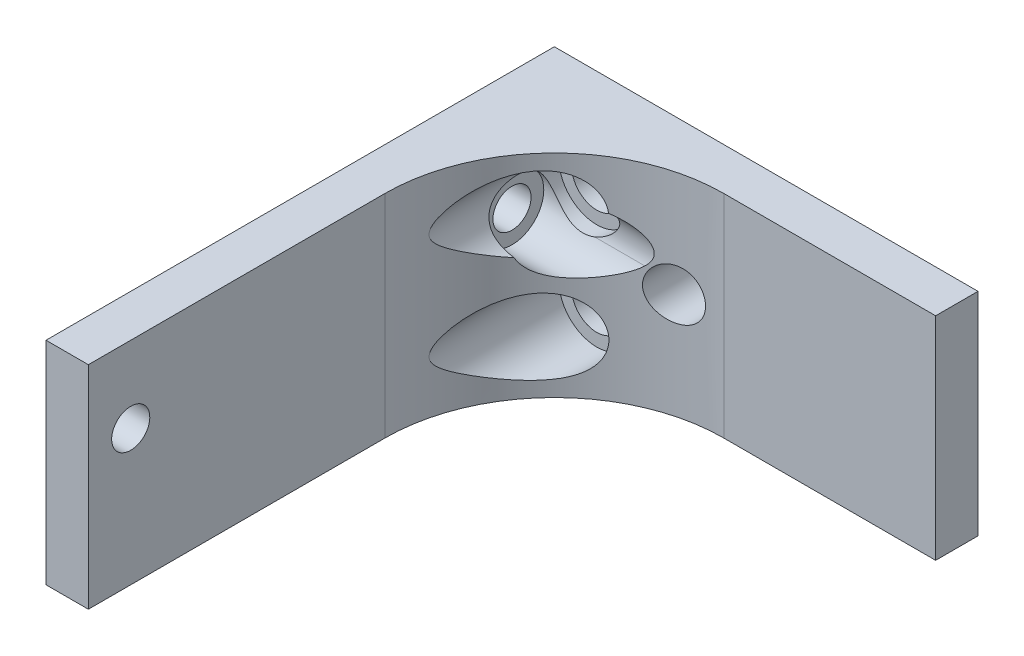
SolidWorks part; units mm, degrees
ref_plane "Alzado" through (0, 0, 0) normal (0, 0, 1) x (1, 0, 0)
ref_plane "Planta" through (0, 0, 0) normal (0, 1, 0) x (1, 0, 0)
ref_plane "Vista lateral" through (0, 0, 0) normal (1, 0, 0) x (0, 0, -1)
sketch "Croquis1" plane through (0, 0, 0) normal (0, 0, 1) x (1, 0, 0)
  line L0 (10, 18.75) -> (10, 6.25) construction
  line L1 (0, 0) -> (50, 0)
  line L2 (0, 0) -> (0, 25)
  line L3 (0, 25) -> (50, 25)
  line L4 (50, 0) -> (50, 25)
  line L6 (0, 25) -> (5, 25)
  line L7 (0, 25) -> (0, 0)
  line L8 (0, 0) -> (5, 0)
  line L9 (5, 25) -> (5, 0)
  circle A0 centre (10, 18.75) radius 2.95
  circle A1 centre (10, 6.25) radius 2.95
  circle A2 centre (20, 12.5) radius 2.95
  point P12 (10, 12.5)
  point P13 (0, 12.5)
  dimension "D3" = 5.9
  dimension "D5" = 10
  dimension "D1" = 50
  dimension "D2" = 25
  dimension "D4" = 12.5
  dimension "D6" = 10
  dimension "D7" = 5
extrude "Saliente-Extruir1" add sketch "Croquis1" along normal blind 5 contours L3 L9 L1 L4 A2 A0 A1 | L9 L3 L2 L1 region at (2.5, 12.5, 0) region at (28.6141, 12.5, 0)
extrude "Saliente-Extruir2" add sketch "Croquis1<3>" along normal blind 60 contours L9 L3 L2 L1 region at (2.5, 12.5, 0)
sketch "Croquis1<3>" plane through (0, 0, 0) normal (0, 0, 1) x (1, 0, 0) same geometry as "Croquis1"
ref_plane "Plano1" through (0, 12.5, 0) normal (0, 1, 0) x (1, 0, 0)
sketch "Croquis2" [suppressed] plane through (0, 12.5, 0) normal (0, 1, 0) x (1, 0, 0)
  line L0 (10, -5) -> (35, -5)
  line L1 (10, -5) -> (50, -5) construction
  line L2 (35, -5) -> (10, -40)
  line L3 (10, -60) -> (10, -5) construction
  line L4 (10, -40) -> (10, -5)
  dimension "D1" = 35
  dimension "D2" = 25
extrude "Saliente-Extruir3" [suppressed] add sketch "Croquis2" along normal blind 2.5 and the other way blind 2.5
sketch "Croquis3" plane through (0, 0, 5) normal (0, 0, 1) x (1, 0, 0)
  circle A0 centre (20, 12.5) radius 2.95 construction
  circle A1 centre (20, 12.5) radius 2.95
extrude "Cortar-Extruir-Lámina2" [suppressed] cut sketch "Croquis3" along normal through all thin thin type mid plane wall 1.5
fillet "Redondeo2" radius 20 1 edges at (5, 12.5, 5)
sketch "Croquis4" plane through (0, 0, 5) normal (0, 0, 1) x (1, 0, 0)
  arc A3 (14.45, 18.75) -> (14.45, 18.75) centre (10, 18.75) ccw
  circle A5 centre (10, 18.75) radius 4.45
  arc A8 (14.45, 6.25) -> (14.45, 6.25) centre (10, 6.25) ccw
  circle A9 centre (10, 6.25) radius 4.45
  dimension "D1" = 1.5
  dimension "D2" = 1.5
extrude "Cortar-Extruir1" cut sketch "Croquis4" along normal through all
sketch "Croquis5" plane through (5, 0, 0) normal (1, 0, 0) x (0, 0, -1)
  line L0 (-12.25, 16) -> (-60, 16) construction
  line L1 (-60, 25) -> (-60, 0) construction
  line L4 (-60, 0) -> (-25, 0)
  line L5 (-60, 0) -> (-25, 0)
  line L6 (-25, 25) -> (-60, 25)
  line L7 (-60, 25) -> (-60, 0)
  line L10 (-25, 25) -> (-60, 25) construction
  line L11 (-60, 25) -> (-60, 0) construction
  line L14 (-25, 0) -> (-25, 25)
  line L15 (-25, 0) -> (-25, 25)
  circle A0 centre (-55, 16) radius 2.25
  circle A1 centre (-10, 16) radius 2.25
  point P10 (-20.5793, 12.5)
  point P11 (0, 0)
  point P12 (-58.768, 16.0847)
  point P13 (-12.25, 16)
  point P14 (-60, 16)
  dimension "D5" = 4.5
  dimension "D2" = 9
  dimension "D3" = 5
  dimension "D4" = 45
  dimension "D1" = 0
extrude "Cortar-Extruir2" cut sketch "Croquis5" against normal through all contours A0 | A1
extrude "Cortar-Extruir-Lámina3" cut sketch "Croquis5<3>" along normal through all thin contours A1 body kept at (0, 25, 60) thin type one direction wall 1.5
sketch "Croquis5<3>" plane through (5, 0, 0) normal (1, 0, 0) x (0, 0, -1) same geometry as "Croquis5"
